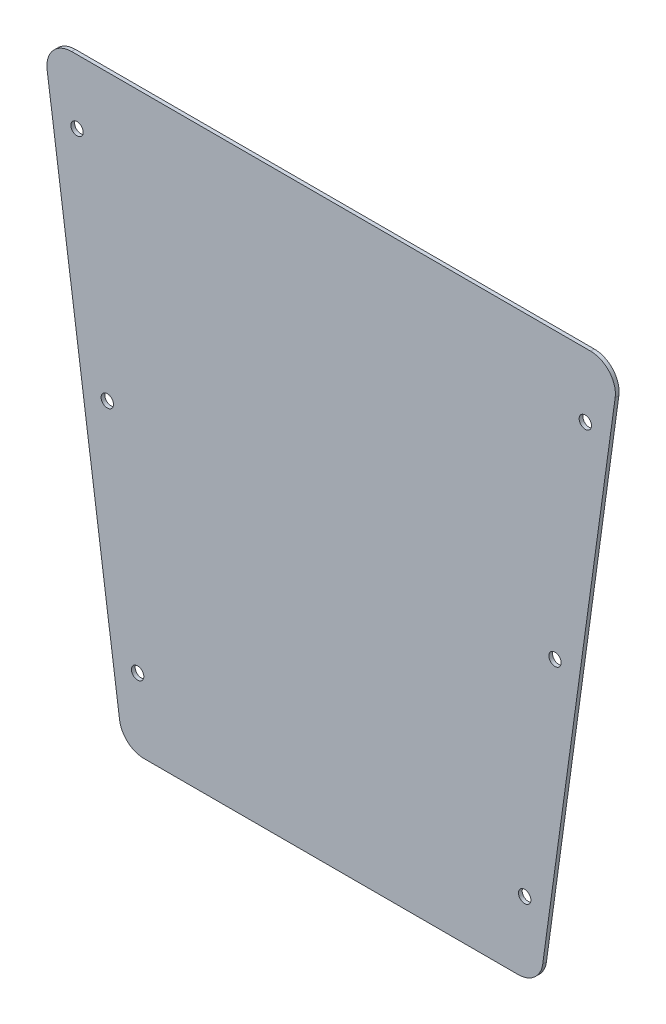
SolidWorks part; units mm, degrees
ref_plane "Front Plane" through (0, 0, 0) normal (0, 0, 1) x (1, 0, 0)
ref_plane "Top Plane" through (0, 0, 0) normal (0, 1, 0) x (1, 0, 0)
ref_plane "Right Plane" through (0, 0, 0) normal (1, 0, 0) x (0, 0, -1)
sketch "Sketch1" plane through (0, 0, 0) normal (0, 0, 1) x (1, 0, 0)
  line L0 (116.3813, -54.7305) -> (-116.3813, -54.7305)
  line L1 (-116.3813, -54.7305) -> (-84.3503, -287.6585)
  line L2 (-84.3503, -287.6585) -> (84.3503, -287.6585)
  line L3 (84.3503, -287.6585) -> (116.3813, -54.7305)
base flange "Base-Flange1" sketch "Sketch1" thickness 1.5 reverse thickness direction no parameters "D1"=3
fillet "Fillet1" radius 10 4 edges at (84.3503, -287.6585, -0.75) (-84.3503, -287.6585, -0.75) (-116.3813, -54.7305, -0.75) (116.3813, -54.7305, -0.75)
sketch "Sketch6" plane through (0, 0, -1.5) normal (0, 0, -1) x (-1, 0, 0)
  circle A0 centre (-102.758, -80.6765) radius 2.5
  circle A1 centre (-90.4971, -169.8374) radius 2.5
  circle A2 centre (-78.2361, -258.9983) radius 2.5
  circle A3 centre (102.7228, -80.6716) radius 2.5
  circle A4 centre (90.4971, -169.8374) radius 2.5
  circle A5 centre (78.2361, -258.9983) radius 2.5
  point P12 (0, 0)
  dimension "D1" = 5
extrude "Cut-Extrude1" cut sketch "Sketch6" against normal blind 10
sketch "Bend-Lines1" [suppressed] plane through (0, 0, 0) normal (0, 1, 0) x (1, 0, 0)
sketch "Bounding-Box1" [suppressed] plane through (0, 0, 0) normal (0, 1, 0) x (1, 0, 0)
sheet metal parameters "Sheet-Metal1" thickness 1.5 parameters "D1"=3
flat pattern "Flat-Pattern1" [suppressed]
sketch "Bend-Lines2" plane through (0, 0, 0) normal (0, 1, 0) x (1, 0, 0)
sketch3d "Bounding-Box2" [suppressed]
  line L0 (114.912, -54.7305, 0) -> (114.912, -287.6585, 0) construction
  line L1 (-114.9121, -54.7305, 0) -> (-114.9121, -287.6585, 0) construction
  line L2 (114.912, -54.7305, 0) -> (-114.9121, -54.7305, 0) construction
  line L3 (114.912, -287.6585, 0) -> (-114.9121, -287.6585, 0) construction
sheet metal parameters "Sheet-Metal2" thickness 1.5 parameters "D1"=3
flat pattern "Flat-Pattern1"
sketch "Bend-Lines2" plane through (0, 0, 0) normal (0, 1, 0) x (1, 0, 0)
sketch3d "Bounding-Box2" [suppressed]
  line L0 (114.912, -54.7305, 0) -> (114.912, -287.6585, 0) construction
  line L1 (-114.9121, -54.7305, 0) -> (-114.9121, -287.6585, 0) construction
  line L2 (114.912, -54.7305, 0) -> (-114.9121, -54.7305, 0) construction
  line L3 (114.912, -287.6585, 0) -> (-114.9121, -287.6585, 0) construction
